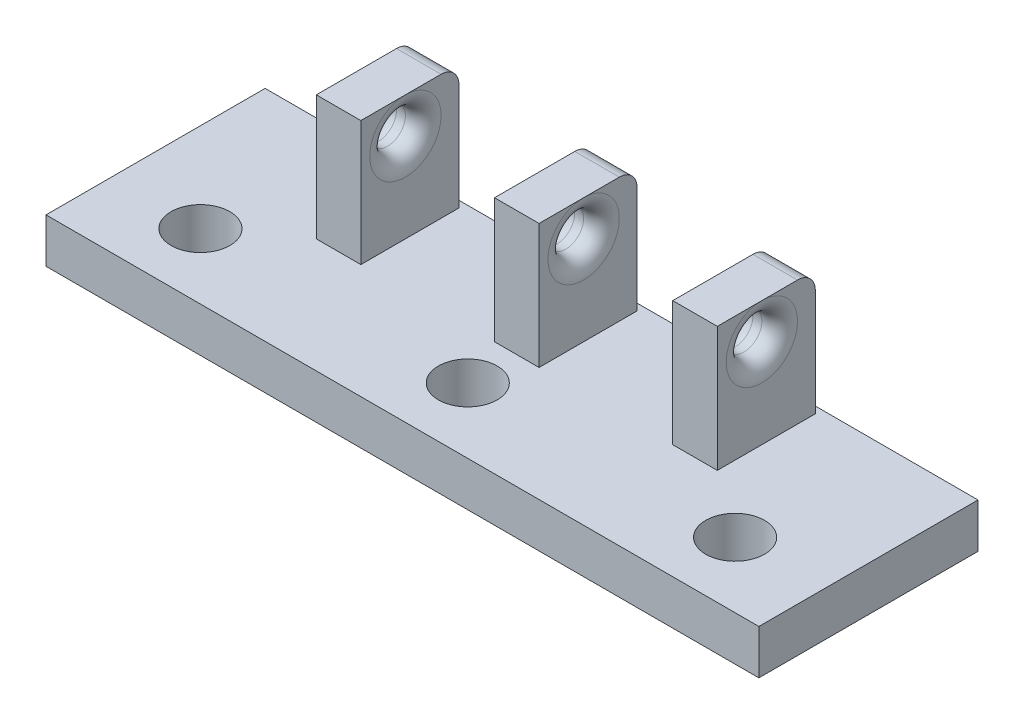
SolidWorks part; units mm, degrees
ref_plane "Front Plane" through (0, 0, 0) normal (0, 0, 1) x (1, 0, 0)
ref_plane "Top Plane" through (0, 0, 0) normal (0, 1, 0) x (1, 0, 0)
ref_plane "Right Plane" through (0, 0, 0) normal (1, 0, 0) x (0, 0, -1)
sketch "Sketch1" plane through (0, 0, 0) normal (0, 1, 0) x (1, 0, 0)
  line L1 (20, -14.6667) -> (-20, -14.6667)
  line L2 (20, -14.6667) -> (20, 14.6667)
  line L3 (20, 14.6667) -> (-20, 14.6667)
  line L4 (-20, -14.6667) -> (-20, 14.6667)
  line L5 (20, -14.6667) -> (-20, 14.6667) construction
  line L6 (20, 14.6667) -> (-20, -14.6667) construction
  circle A0 centre (-15, 11) radius 1.65
  circle A1 centre (0, 11) radius 1.65
  circle A2 centre (15, 11) radius 1.65
  circle A3 centre (0, 0) radius 1.65
  circle A4 centre (15, 0) radius 1.65
  circle A5 centre (0, -11) radius 1.65
  circle A6 centre (15, -11) radius 1.65
  circle A7 centre (-15, 0) radius 1.65
  circle A8 centre (-15, -11) radius 1.65
  point P0 (0, 0)
  dimension "D1" = 3.3
  dimension "D6" = 40
  dimension "D2" = 15
  dimension "D3" = 11
  dimension "D4" = 3
  dimension "D5" = 3
extrude "Boss-Extrude1" add sketch "Sketch1" along normal blind 2.5
sketch "Sketch2" plane through (0, 2.5, 0) normal (0, 1, 0) x (1, 0, 0)
  line L0 (0, 0) -> (0, -11) construction
  line L1 (8.75, -8.25) -> (11.25, -8.25)
  line L2 (-1.25, -8.25) -> (1.25, -8.25)
  line L3 (-1.25, -8.25) -> (-1.25, -2.75)
  line L4 (-1.25, -2.75) -> (1.25, -2.75)
  line L5 (1.25, -8.25) -> (1.25, -2.75)
  line L6 (-1.25, -8.25) -> (1.25, -2.75) construction
  line L7 (-1.25, -2.75) -> (1.25, -8.25) construction
  line L8 (8.75, -8.25) -> (8.75, -2.75)
  line L9 (8.75, -2.75) -> (11.25, -2.75)
  line L10 (11.25, -8.25) -> (11.25, -2.75)
  line L11 (8.75, -8.25) -> (11.25, -2.75) construction
  line L12 (8.75, -2.75) -> (11.25, -8.25) construction
  line L13 (-10, -5.5) -> (10, -5.5) construction
  line L14 (-8.75, -2.75) -> (-11.25, -8.25) construction
  line L15 (-8.75, -8.25) -> (-11.25, -2.75) construction
  line L16 (-11.25, -8.25) -> (-11.25, -2.75)
  line L17 (-8.75, -2.75) -> (-11.25, -2.75)
  line L18 (-8.75, -8.25) -> (-8.75, -2.75)
  line L19 (-8.75, -8.25) -> (-11.25, -8.25)
  circle A0 centre (0, -11) radius 2.75 construction
  circle A1 centre (-15, -11) radius 2.75 construction
  circle A2 centre (15, -11) radius 2.75 construction
  circle A3 centre (0, 0) radius 2.75 construction
  circle A4 centre (-15, 0) radius 2.75 construction
  circle A5 centre (15, 0) radius 2.75 construction
  point P13 (0, -5.5)
  point P19 (10, -5.5)
  point P26 (0, -5.5)
  point P30 (-10, -5.5)
  dimension "D1" = 5.5
  dimension "D2" = 5.5
  dimension "D3" = 2.5
  dimension "D4" = 5.5
  dimension "D6" = 10
  dimension "D5" = 2
extrude "Boss-Extrude2" add sketch "Sketch2" along normal blind 7
sketch "Sketch3" plane through (11.25, 0, 0) normal (1, 0, 0) x (0, 0, -1)
  line L1 (-2.75, 9.5) -> (-2.75, 2.5) construction
  line L2 (-8.25, 9.5) -> (-2.75, 9.5) construction
  circle A0 centre (-5.75, 7.5) radius 1
  point P3 (-4.75, 7.5)
  point P6 (-5.75, 8.5)
  dimension "D1" = 2
  dimension "D2" = 2
  dimension "D3" = 1
extrude "Cut-Extrude1" cut sketch "Sketch3" against normal up to surface (22.5 mm away) up to face at (-11.25, 6, 5.5)
fillet "Fillet1" radius 1 6 edges at (-8.75, 7.5, 6.75) (-11.25, 7.5, 4.75) (1.25, 7.5, 6.75) (-1.25, 7.5, 4.75) (8.75, 7.5, 4.75) (11.25, 7.5, 4.75)
fillet "Fillet2" radius 1 3 edges at (0, 9.5, 2.75) (-10, 9.5, 2.75) (10, 9.5, 2.75)
sketch "Sketch4" plane through (0, 2.5, 0) normal (0, 1, 0) x (1, 0, 0)
  line L0 (-20, -2.3721) -> (20, -2.3721)
  line L1 (-20, 14.6667) -> (-20, -14.6667) construction
  line L2 (20, -14.6667) -> (20, 14.6667) construction
  line L3 (-20, -2.3721) -> (-20, 14.6667)
  line L4 (-20, 14.6667) -> (20, 14.6667)
  line L5 (20, 14.6667) -> (20, -2.3721)
extrude "Cut-Extrude2" cut sketch "Sketch4" against normal up to next
